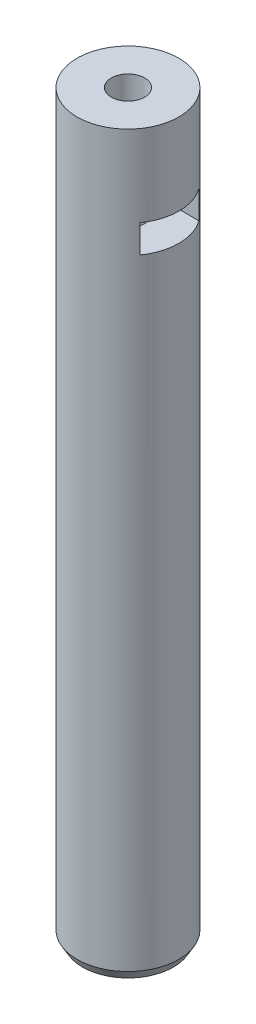
SolidWorks part; units mm, degrees
ref_plane "Front Plane" through (0, 0, 0) normal (0, 0, 1) x (1, 0, 0)
ref_plane "Top Plane" through (0, 0, 0) normal (0, 1, 0) x (1, 0, 0)
ref_plane "Right Plane" through (0, 0, 0) normal (1, 0, 0) x (0, 0, -1)
sketch "Sketch2" plane through (0, 0, 0) normal (0, 1, 0) x (1, 0, 0)
  circle A0 centre (0, 0) radius 9.3
  dimension "D1" = 18.6
extrude "Boss-Extrude1" add sketch "Sketch2" along normal blind 135
sketch "Sketch3" plane through (0, 135, 0) normal (0, 1, 0) x (1, 0, 0)
  circle A0 centre (0, 0) radius 3.05
  dimension "D1" = 6.1
chamfer "Chamfer1" distance 1 angle 60 1 edges at (0, 0, 9.3) first distance on face at (0, 0, 9.3)
extrude "Cut-Extrude1" cut sketch "Sketch3" against normal blind 25
ref_plane "Plane1" through (0, 115, 0) normal (0, 1, 0) x (1, 0, 0)
sketch "Sketch4" plane through (0, 115, 0) normal (0, 1, 0) x (1, 0, 0)
  line L0 (9.3, 0) -> (-9.3, 0) construction
  line L14 (3.12, 5.404) -> (7.5688, 5.404)
  line L16 (3.12, 5.404) -> (-3.12, 5.404)
  line L17 (-3.12, 5.404) -> (-6.24, 0)
  line L18 (-6.24, 0) -> (-3.12, -5.404)
  line L19 (-3.12, -5.404) -> (3.12, -5.404)
  line L21 (3.12, -5.404) -> (7.5688, -5.404)
  line L23 (6.24, 0) -> (4.68, 2.702) [skipped]
  line L24 (3.12, -5.404) -> (4.68, -2.702) [skipped]
  circle A0 centre (0, 0) radius 9.3 construction
  arc A2 (0, 5.404) -> (0, -5.404) centre (0, 0) ccw construction
  arc A3 (7.5688, -5.404) -> (7.5688, 5.404) centre (0, 0) ccw
  dimension "D1" = 6.24
extrude "Cut-Extrude2" cut sketch "Sketch4" along normal blind 5.1
